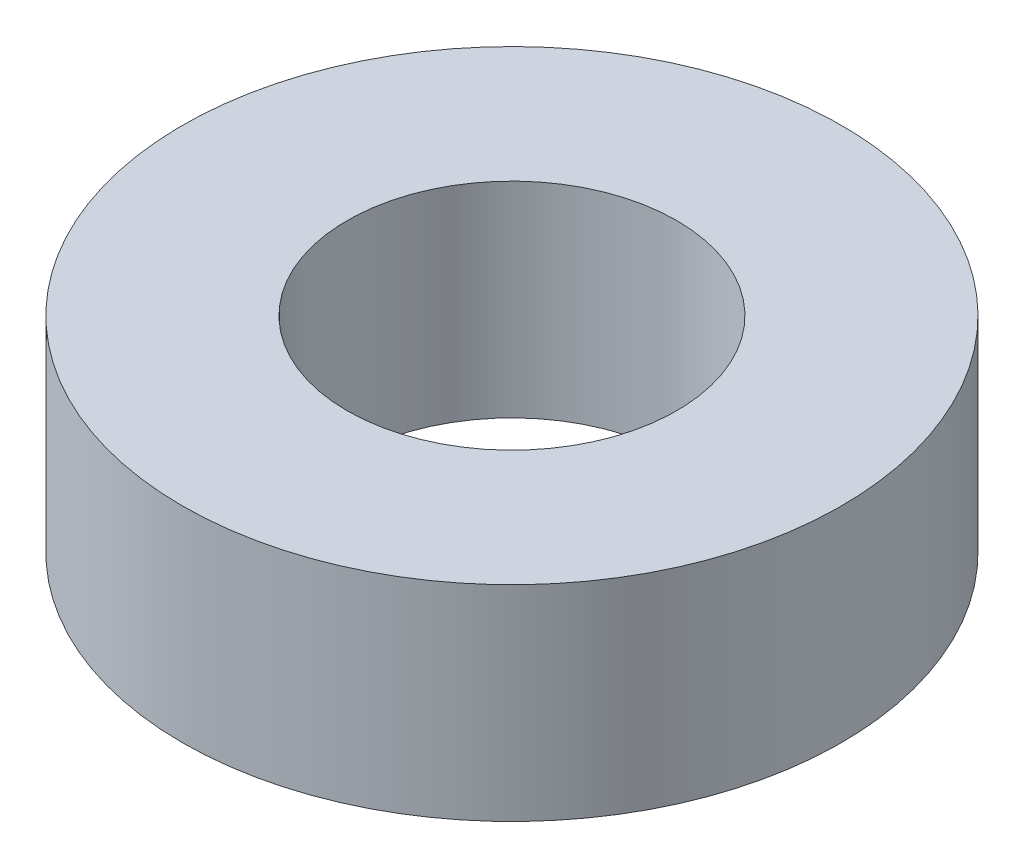
SolidWorks part; units mm, degrees
ref_plane "Front Plane" through (0, 0, 0) normal (0, 0, 1) x (1, 0, 0)
ref_plane "Top Plane" through (0, 0, 0) normal (0, 1, 0) x (1, 0, 0)
ref_plane "Right Plane" through (0, 0, 0) normal (1, 0, 0) x (0, 0, -1)
sketch "Sketch1" plane through (0, 0, 0) normal (0, 1, 0) x (1, 0, 0)
  circle A0 centre (0, 0) radius 45
  dimension "FLANGE_OD" = 90
extrude "Boss-Extrude1" add sketch "Sketch1" along normal blind 28
sketch "Sketch2" plane through (0, 0, 0) normal (0, 1, 0) x (1, 0, 0)
  circle A0 centre (0, 0) radius 22.5
  dimension "BORE_D" = 45
extrude "Cut-Extrude1" cut sketch "Sketch2" along normal through all
sketch "Sketch3" plane through (0, 28, 0) normal (0, 1, 0) x (1, 0, 0)
  circle A0 centre (0, 0) radius 16.7967 construction
  circle A1 centre (-16.7967, 0) radius 2.8819
  dimension "BOLT_D" = 5.7637
  dimension "BOLT_PCD" = 33.5934
extrude "Cut-Extrude2" cut sketch "Sketch3" against normal blind 22.0753 rebuild error yes
pattern_circular "CirPattern1" count 4 over 360 rebuild error yes
